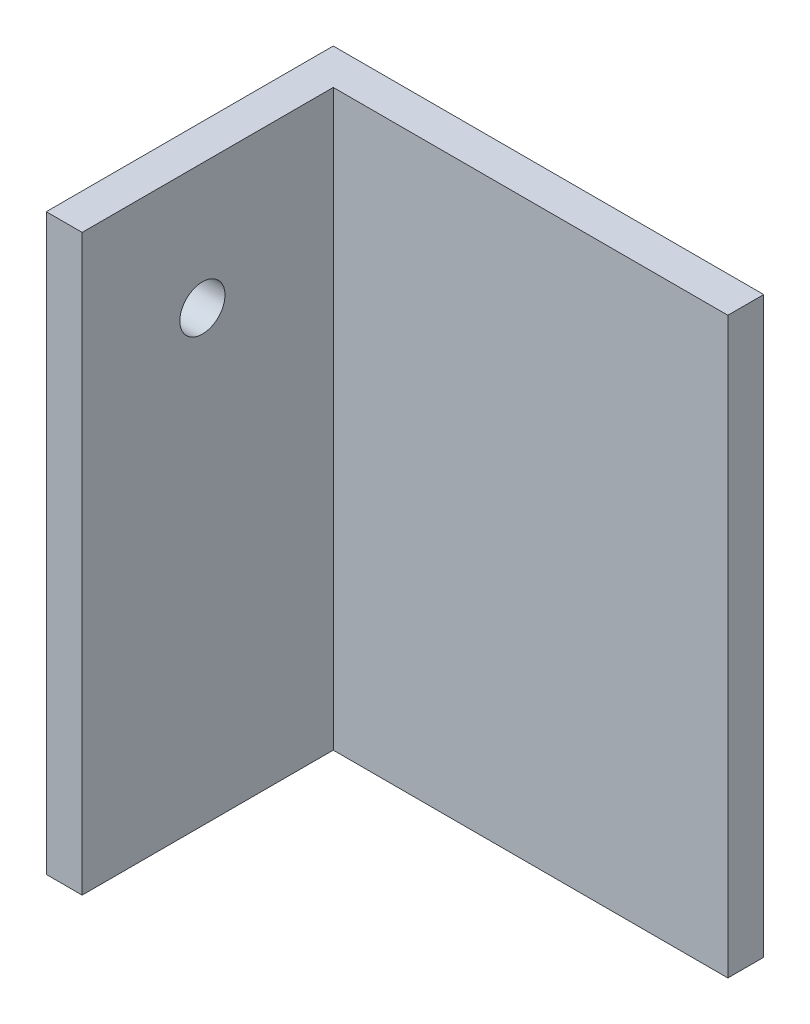
SolidWorks part; units mm, degrees
ref_plane "Front" through (0, 0, 0) normal (0, 0, 1) x (1, 0, 0)
ref_plane "Top" through (0, 0, 0) normal (0, 1, 0) x (1, 0, 0)
ref_plane "Right" through (0, 0, 0) normal (1, 0, 0) x (0, 0, -1)
sketch "Sketch1" plane through (0, 0, 0) normal (0, 1, 0) x (1, 0, 0)
  line L0 (-19.05, -12.7) -> (-15.875, -12.7)
  line L1 (-19.05, -12.7) -> (19.05, -12.7) construction
  line L2 (-19.05, -12.7) -> (-19.05, 12.7)
  line L3 (-19.05, 12.7) -> (19.05, 12.7)
  line L4 (19.05, -12.7) -> (19.05, 12.7) construction
  line L5 (-19.05, -12.7) -> (19.05, 12.7) construction
  line L6 (-19.05, 12.7) -> (19.05, -12.7) construction
  line L7 (-15.875, -12.7) -> (-15.875, 9.525)
  line L8 (-15.875, 9.525) -> (19.05, 9.525)
  line L9 (19.05, 9.525) -> (19.05, 12.7)
  point P0 (0, 0)
  point P6 (-20.3481, 6.6657)
  point P10 (0, -12.7)
  dimension "D1" = 38.1
  dimension "D2" = 25.4
  dimension "D3" = 34.925
  dimension "D4" = 22.225
extrude "Boss-Extrude1" add sketch "Sketch1" along normal mid plane 50.8
sketch "Sketch2" plane through (-19.05, 0, 0) normal (-1, 0, 0) x (0, 0, 1)
  line L0 (-9.525, 25.4) -> (-9.525, -25.4) construction
  line L1 (-12.7, 25.4) -> (12.7, 25.4) construction
  line L2 (-12.7, -25.4) -> (12.7, -25.4) construction
  line L3 (12.7, 25.4) -> (12.7, -25.4) construction
  line L4 (-9.525, 25.4) -> (12.7, 25.4) construction
  line L5 (-9.525, 25.4) -> (-9.525, 3.175) construction
  line L6 (-9.525, 3.175) -> (12.7, 3.175) construction
  line L7 (12.7, 25.4) -> (12.7, 3.175) construction
  line L9 (-4.445, 25.4) -> (-4.445, -25.4) construction
  circle A0 centre (2.055, 14.2875) radius 2
  point P14 (12.7, 14.2875)
  point P18 (-9.525, -23.8555)
  dimension "D1" = 4
  dimension "D2" = 5.08
  dimension "D3" = 6.5
extrude "Cut-Extrude1" cut sketch "Sketch2" against normal through all
